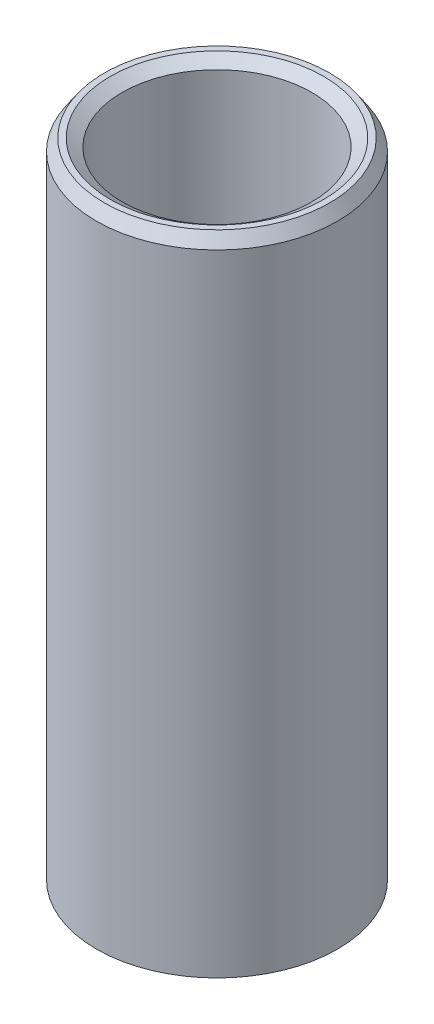
SolidWorks part; units mm, degrees
ref_plane "Front Plane" through (0, 0, 0) normal (0, 0, 1) x (1, 0, 0)
ref_plane "Top Plane" through (0, 0, 0) normal (0, 1, 0) x (1, 0, 0)
ref_plane "Right Plane" through (0, 0, 0) normal (1, 0, 0) x (0, 0, -1)
sketch "Sketch1" plane through (0, 0, 0) normal (0, 1, 0) x (1, 0, 0)
  circle A0 centre (0, 0) radius 30
  dimension "SLEEVE_OD" = 60
extrude "Boss-Extrude1" add sketch "Sketch1" along normal blind 161.7526
sketch "Sketch2" plane through (0, 0, 0) normal (0, 1, 0) x (1, 0, 0)
  circle A0 centre (0, 0) radius 23.597
  dimension "BORE_D" = 47.1939
extrude "Cut-Extrude1" cut sketch "Sketch2" along normal through all
chamfer "Chamfer1" distance 2.9366 angle 34.087 4 edges at (0, 161.7526, 23.597) (0, 0, 23.597) (0, 0, 30) (0, 161.7526, 30) first distance on face at (0, 161.7526, 23.597) first distance on face at (0, 0, 23.597) first distance on face at (0, 161.7526, 30)
